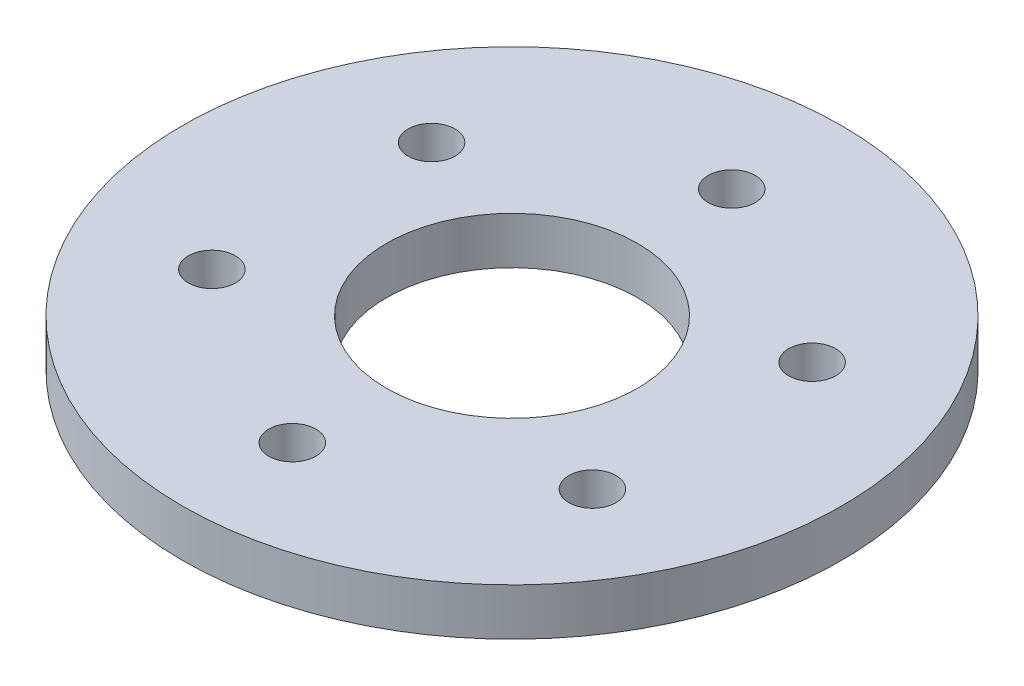
SolidWorks part; units mm, degrees
ref_plane "前视基准面" through (0, 0, 0) normal (0, 0, 1) x (1, 0, 0)
ref_plane "上视基准面" through (0, 0, 0) normal (0, 1, 0) x (1, 0, 0)
ref_plane "右视基准面" through (0, 0, 0) normal (1, 0, 0) x (0, 0, -1)
ref_axis "x轴" through (88.99, 0, 0) along (-1, 0, 0)
ref_axis "y轴" through (0, 0, -88.99) along (0, 0, 1)
ref_axis "z轴" through (0, -44, 0) along (0, 1, 0)
sketch "草图1" plane through (0, 0, 0) normal (0, 1, 0) x (1, 0, 0)
  circle A0 centre (0, 0) radius 21
  circle A1 centre (0, 0) radius 14 construction
  circle A2 centre (0, 14) radius 1.5
  circle A3 centre (12.1244, 7) radius 1.5
  circle A4 centre (12.1244, -7) radius 1.5
  circle A5 centre (0, -14) radius 1.5
  circle A6 centre (-12.1244, -7) radius 1.5
  circle A7 centre (-12.1244, 7) radius 1.5
  circle A8 centre (0, 0) radius 8
  point P18 (0, 0)
  dimension "D1" = 6
extrude "凸台-拉伸1" add sketch "草图1" along normal blind 3
